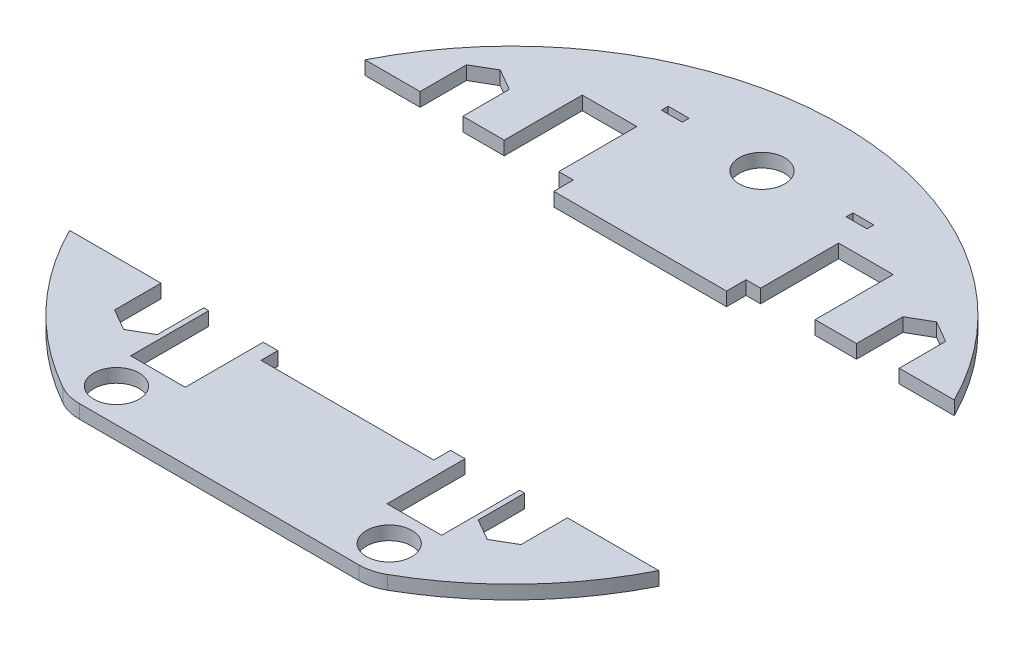
SolidWorks part; units mm, degrees
ref_plane "Front Plane" through (0, 0, 0) normal (0, 0, 1) x (1, 0, 0)
ref_plane "Top Plane" through (0, 0, 0) normal (0, 1, 0) x (1, 0, 0)
ref_plane "Right Plane" through (0, 0, 0) normal (1, 0, 0) x (0, 0, -1)
sketch "Sketch1" plane through (0, 0, 0) normal (0, 1, 0) x (1, 0, 0)
  line L0 (-30.7634, -64.4046) -> (30.7634, -64.4046)
  line L1 (0, -83.2398) -> (0, 0) construction
  line L2 (0, -83.2398) -> (33.2911, -64.4046) construction
  arc A0 (35.6856, -63.1093) -> (-35.6856, -63.1093) centre (0, 0) ccw
  circle A1 centre (0, -83.2398) radius 38.25 construction
  arc A2 (30.7634, -64.4046) -> (35.6856, -63.1093) centre (30.7634, -54.4046) ccw
  arc A3 (-30.7634, -64.4046) -> (-35.6856, -63.1093) centre (-30.7634, -54.4046) cw
  dimension "D1" = 145
  dimension "D2" = 76.5
  dimension "D4" = 10
  dimension "D3" = 60.5
extrude "Boss-Extrude1" add sketch "Sketch1" along normal blind 3
sketch "Sketch2" plane through (0, 3, 0) normal (0, 1, 0) x (1, 0, 0)
  line L0 (18, -36.2) -> (-18, -36.2) construction
  line L1 (-34.2, -49.6757) -> (-22.2, -49.6757)
  line L2 (-34.2, -49.6757) -> (-34.2, 49.6757)
  line L3 (-34.2, 49.6757) -> (-22.2, 49.6757)
  line L4 (-22.2, -49.6757) -> (-22.2, -32.5)
  line L5 (-19, -32.5) -> (-22.2, -32.5) construction
  line L6 (-22.2, -49.6757) -> (-22.2, -32.5)
  line L7 (-19, -32.5) -> (-22.2, -32.5)
  line L8 (19, 28.2) -> (-19, 28.2) construction
  line L9 (18, -36.2) -> (-18, -36.2)
  line L10 (-19, 32.5) -> (-22.2, 32.5) construction
  line L11 (-19, 32.5) -> (-22.2, 32.5)
  line L12 (19, 28.2) -> (-19, 28.2)
  line L13 (-19, -32.5) -> (-19, -36.2)
  line L14 (-19, -36.2) -> (-18, -36.2)
  line L15 (-19, 32.5) -> (-19, 28.2)
  line L16 (-22.2, 32.5) -> (-22.2, 49.6757)
  line L17 (0, 0) -> (0, -64.4046) construction
  line L18 (-30.7634, -64.4046) -> (30.7634, -64.4046) construction
  line L19 (22.2, 32.5) -> (22.2, 49.6757)
  line L20 (19, 32.5) -> (19, 28.2)
  line L21 (19, -36.2) -> (18, -36.2)
  line L22 (19, -32.5) -> (19, -36.2)
  line L23 (19, 32.5) -> (22.2, 32.5)
  line L24 (19, -32.5) -> (22.2, -32.5)
  line L25 (22.2, -49.6757) -> (22.2, -32.5)
  line L26 (22.2, -49.6757) -> (22.2, -32.5)
  line L27 (34.2, 49.6757) -> (22.2, 49.6757)
  line L28 (34.2, -49.6757) -> (34.2, 49.6757)
  line L29 (34.2, -49.6757) -> (22.2, -49.6757)
extrude "Cut-Extrude1" cut sketch "Sketch2" against normal through all contours L29 L28 L27 L19 L23 L20 L12 L15 L11 L16 L3 L2 L1 L4 L7 L13 L14 L9 L21 L22 L24 L25 region at (0, 3, 1.8654)
sketch "Sketch3" plane through (0, 3, 0) normal (0, 1, 0) x (1, 0, 0)
  line L0 (-34.2, 32.5) -> (-34.2, -32.5)
  line L1 (-72.5, -32.5) -> (-34.2, -32.5)
  line L2 (-72.5, -32.5) -> (-72.5, 32.5)
  line L3 (-72.5, 32.5) -> (-34.2, 32.5)
  line L4 (72.5, -32.5) -> (72.5, 32.5)
  line L5 (-72.5, -32.5) -> (72.5, 32.5) construction
  line L6 (-72.5, 32.5) -> (72.5, -32.5) construction
  line L7 (-34.2, -49.6757) -> (-34.2, 49.6757) construction
  line L8 (34.2, 32.5) -> (34.2, -32.5)
  line L9 (34.2, -49.6757) -> (34.2, 49.6757) construction
  line L10 (34.2, 32.5) -> (72.5, 32.5)
  line L11 (34.2, -32.5) -> (72.5, -32.5)
  arc A0 (35.6856, -63.1093) -> (-35.6856, -63.1093) centre (0, 0) ccw construction
  point P0 (0, 0)
  dimension "D1" = 65
extrude "Cut-Extrude2" cut sketch "Sketch3" against normal through all
sketch "Sketch4" plane through (0, 3, 0) normal (0, 1, 0) x (1, 0, 0)
  line L0 (0, 0) -> (0, -20.7985) construction
  circle A0 centre (30, -57) radius 5
  circle A4 centre (-30, -57) radius 5
  dimension "D3" = 10
  dimension "D1" = 57
  dimension "D2" = 30
extrude "Cut-Extrude3" cut sketch "Sketch4" against normal through all
sketch "Sketch5" plane through (0, 3, 0) normal (0, 1, 0) x (1, 0, 0)
  line L0 (-52.7, 37.2865) -> (-52.7, 32.5)
  line L2 (-34.2, 32.5) -> (-64.8074, 32.5) construction
  line L3 (-52.7, 32.5) -> (-43.3, 32.5)
  line L4 (-43.3, 32.5) -> (-43.3, 37.2865)
  line L6 (-44.7, -37.2865) -> (-44.7, -32.5)
  line L7 (-64.8074, -32.5) -> (-34.2, -32.5) construction
  line L8 (0, 0) -> (0, -64.4046) construction
  line L9 (-30.7634, -64.4046) -> (30.7634, -64.4046) construction
  line L16 (-35.3, -37.2865) -> (-35.3, -32.5)
  line L17 (-43.3, 42.7135) -> (-48, 45.4271)
  line L18 (-48, 45.4271) -> (-52.7, 42.7135)
  line L19 (-52.7, 42.7135) -> (-52.7, 37.2865)
  line L20 (-52.7, 37.2865) -> (-48, 34.5729) construction
  line L21 (-48, 34.5729) -> (-43.3, 37.2865) construction
  line L22 (-43.3, 37.2865) -> (-43.3, 42.7135)
  line L23 (-40, -34.5729) -> (-44.7, -37.2865) construction
  line L24 (-44.7, -37.2865) -> (-44.7, -42.7135)
  line L25 (-44.7, -42.7135) -> (-40, -45.4271)
  line L26 (-40, -45.4271) -> (-35.3, -42.7135)
  line L27 (-35.3, -42.7135) -> (-35.3, -37.2865)
  line L28 (-35.3, -37.2865) -> (-40, -34.5729) construction
  line L30 (-35.3, -32.5) -> (-44.7, -32.5)
  line L31 (35.3, -37.2865) -> (40, -34.5729) construction
  line L32 (40, -34.5729) -> (44.7, -37.2865) construction
  line L33 (48, 34.5729) -> (43.3, 37.2865) construction
  line L34 (52.7, 37.2865) -> (48, 34.5729) construction
  line L35 (35.3, -32.5) -> (44.7, -32.5)
  line L36 (35.3, -42.7135) -> (35.3, -37.2865)
  line L37 (40, -45.4271) -> (35.3, -42.7135)
  line L38 (44.7, -42.7135) -> (40, -45.4271)
  line L39 (44.7, -37.2865) -> (44.7, -42.7135)
  line L40 (43.3, 37.2865) -> (43.3, 42.7135)
  line L41 (52.7, 42.7135) -> (52.7, 37.2865)
  line L42 (48, 45.4271) -> (52.7, 42.7135)
  line L43 (43.3, 42.7135) -> (48, 45.4271)
  line L44 (35.3, -37.2865) -> (35.3, -32.5)
  line L45 (44.7, -37.2865) -> (44.7, -32.5)
  line L46 (43.3, 32.5) -> (43.3, 37.2865)
  line L47 (52.7, 32.5) -> (43.3, 32.5)
  line L48 (52.7, 37.2865) -> (52.7, 32.5)
  circle A2 centre (-48, 40) radius 4.7 construction
  circle A3 centre (-40, -40) radius 4.7 construction
  circle A4 centre (40, -40) radius 4.7 construction
  circle A5 centre (48, 40) radius 4.7 construction
  dimension "D1" = 9.4
  dimension "D2" = 48
  dimension "D3" = 40
  dimension "D4" = 40
  dimension "D5" = 40
  dimension "D6" = 9.4
extrude "Cut-Extrude4" cut sketch "Sketch5" against normal through all
sketch "Sketch6" plane through (0, 3, 0) normal (0, 1, 0) x (1, 0, 0)
  line L4 (-18.02, 55.5) -> (-18.02, 57)
  line L5 (-22.62, 55.5) -> (-18.02, 55.5)
  line L6 (-22.62, 57) -> (-22.62, 55.5)
  line L7 (-18.02, 57) -> (-22.62, 57)
  line L8 (-18.02, 55.5) -> (-18.02, 57)
  line L9 (-22.62, 55.5) -> (-18.02, 55.5)
  line L10 (-22.62, 57) -> (-22.62, 55.5)
  line L11 (-18.02, 57) -> (-22.62, 57)
  line L12 (22.62, 57) -> (18.02, 57)
  line L13 (18.02, 57) -> (18.02, 55.5)
  line L14 (18.02, 55.5) -> (22.62, 55.5)
  line L15 (22.62, 55.5) -> (22.62, 57)
  line L16 (22.62, 57) -> (18.02, 57)
  line L17 (18.02, 57) -> (18.02, 55.5)
  line L18 (18.02, 55.5) -> (22.62, 55.5)
  line L19 (22.62, 55.5) -> (22.62, 57)
  dimension "D1" = 0
  dimension "D2" = 0
extrude "Cut-Extrude5" cut sketch "Sketch6" against normal through all
sketch "Sketch7" plane through (0, 3, 0) normal (0, 1, 0) x (1, 0, 0)
  line L0 (0, 0) -> (0, 55) construction
  circle A0 centre (0, 55) radius 5
  dimension "D1" = 10
  dimension "D2" = 55
extrude "Cut-Extrude6" cut sketch "Sketch7" against normal through all
equation "\"smallPulleyTeeth\"= 30"
equation "\"largePulleyTeeth\"= 30"
equation "\"eighthThick\"= 3.0mm"
equation "\"sixteenthThick\"= 1.7mm"
equation "\"quarterThick\"=6.0mm"
equation "\"OD\"= 145mm"
equation "\"puckAngle\"= 60.5deg"
equation "\"puckDiam\"= 76.5mm"
equation "\"axlePress\"= 5.9mm"
equation "\"press\"= 0.2mm"
equation "\"wheelClear\"= 0.3mm"
equation "\"10-32clear\"= 4.8mm"
equation "\"6-32clear\"= 3.3mm"
equation "\"8-32clear\"= 4.0mm"
equation "\"4-40clear\"= 3.0mm"
equation "\"wheelHeight\"= 22mm"
equation "\"wheelWell\"= 65mm"
equation "\"D1@Sketch1\"=\"OD\""
equation "\"D1@Boss-Extrude1\"=\"eighthThick\""
equation "\"D2@Sketch1\"=\"puckDiam\""
equation "\"D3@Sketch1\"=\"puckAngle\""
equation "\"D1@Sketch3\"=\"wheelWell\""
